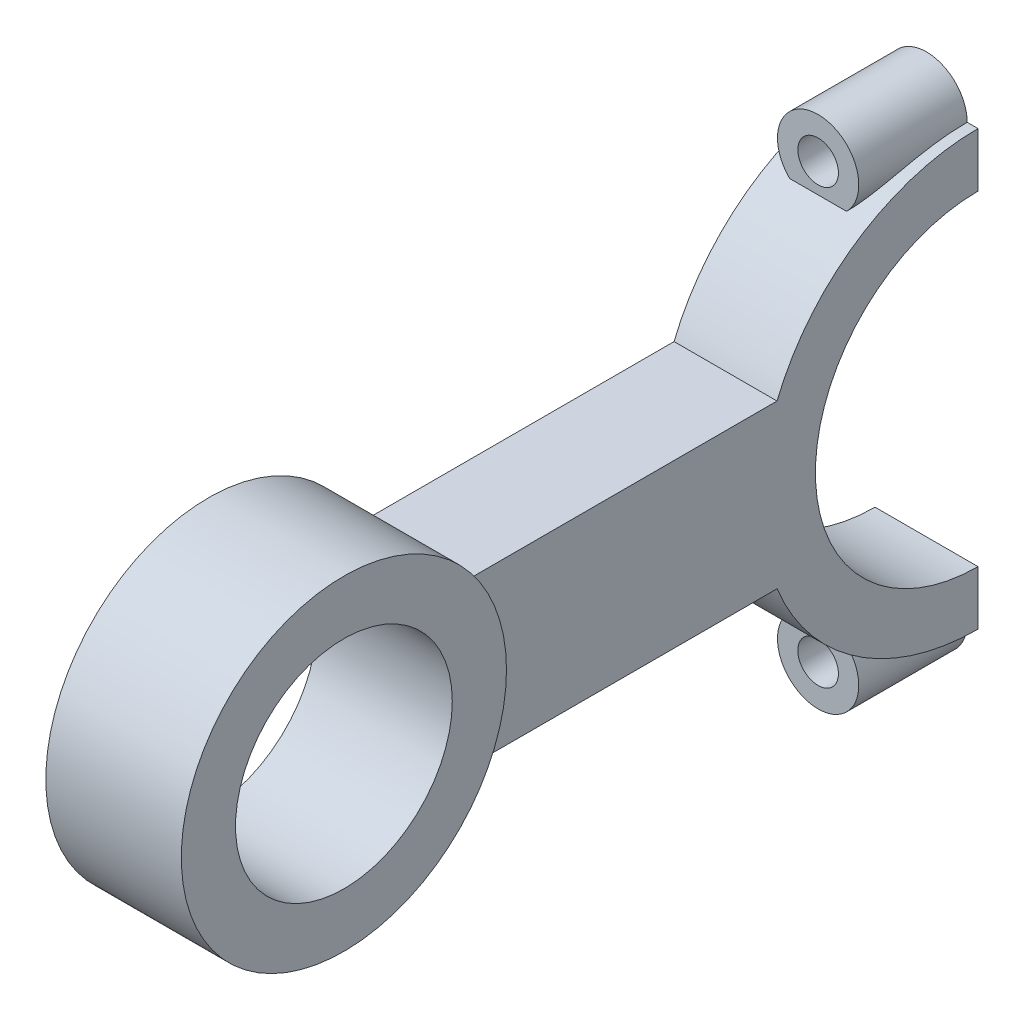
SolidWorks part; units mm, degrees
ref_plane "Front Plane" through (0, 0, 0) normal (0, 0, 1) x (1, 0, 0)
ref_plane "Top Plane" through (0, 0, 0) normal (0, 1, 0) x (1, 0, 0)
ref_plane "Right Plane" through (0, 0, 0) normal (1, 0, 0) x (0, 0, -1)
sketch "Sketch1" plane through (0, 0, 0) normal (1, 0, 0) x (0, 0, -1)
  line L0 (76.2, 0) -> (-76.2, 0) construction
  line L1 (59.3995, -19.05) -> (-59.3995, -19.05)
  line L2 (59.3995, -19.05) -> (59.3995, 19.05) construction
  line L3 (59.3995, 19.05) -> (-59.3995, 19.05)
  line L4 (-59.3995, -19.05) -> (-59.3995, 19.05) construction
  line L5 (59.3995, -19.05) -> (-59.3995, 19.05) construction
  line L6 (59.3995, 19.05) -> (-59.3995, -19.05) construction
  line L7 (76.2, 50.8) -> (76.2, 38.1)
  line L8 (76.2, -38.1) -> (76.2, -50.8)
  circle A0 centre (-76.2, 0) radius 25.4
  circle A1 centre (-76.2, 0) radius 38.1
  arc A2 (76.2, 38.1) -> (76.2, -38.1) centre (76.2, 0) ccw
  arc A3 (76.2, 50.8) -> (76.2, -50.8) centre (76.2, 0) ccw
  circle A4 centre (76.2, 0) radius 38.1 construction
  circle A5 centre (76.2, 0) radius 50.8 construction
  point P0 (0, 0)
  dimension "D3" = 50.8
  dimension "D5" = 76.2
  dimension "D1" = 152.4
  dimension "D2" = 38.1
  dimension "D4" = 12.7
  dimension "D6" = 12.7
extrude "Boss-Extrude2" add sketch "Sketch1" against normal mid plane 24.13 contours L3 A1 L1 A0 | L1 A1 L3 A0 | A3 L3 A1 L1 | L3 A3 L1 A2 | L7 A3 L3 A2 | L1 A3 L8 A2 region at (0, -35.8824, -53.4043) region at (0, 0, -33.2254) region at (0, 0, 6.576) region at (0, 35.8824, -53.4043) region at (0, 0, 113.2578) region at (0, 0, 46.7377)
extrude "Boss-Extrude3" add sketch "Sketch1<6>" along normal mid plane 31.75 contours A1 | A0
sketch "Sketch1<6>" plane through (0, 0, 0) normal (1, 0, 0) x (0, 0, -1) same geometry as "Sketch1"
sketch "Sketch3" plane through (0, 0, -76.2) normal (0, 0, -1) x (-1, 0, 0)
  line L0 (12.065, -50.8) -> (-12.065, -50.8) construction
  circle A0 centre (0, -50.8) radius 9.525
  dimension "D1" = 19.05
extrude "Boss-Extrude4" add sketch "Sketch3" against normal blind 25.4
sketch "Sketch5" plane through (0, 0, -76.2) normal (0, 0, -1) x (-1, 0, 0)
  circle A0 centre (0, -50.8) radius 4.76
  arc A1 (-9.525, -50.8) -> (9.525, -50.8) centre (0, -50.8) ccw construction
  dimension "D1" = 9.52
extrude "Cut-Extrude1" cut sketch "Sketch5" against normal blind 32.4
mirror "Mirror2" about plane through (0, 0, 0) normal (0, 1, 0) of "Boss-Extrude4", "Cut-Extrude1"
sketch "Sketch7" plane through (12.065, 0, 0) normal (1, 0, 0) x (0, 0, -1)
